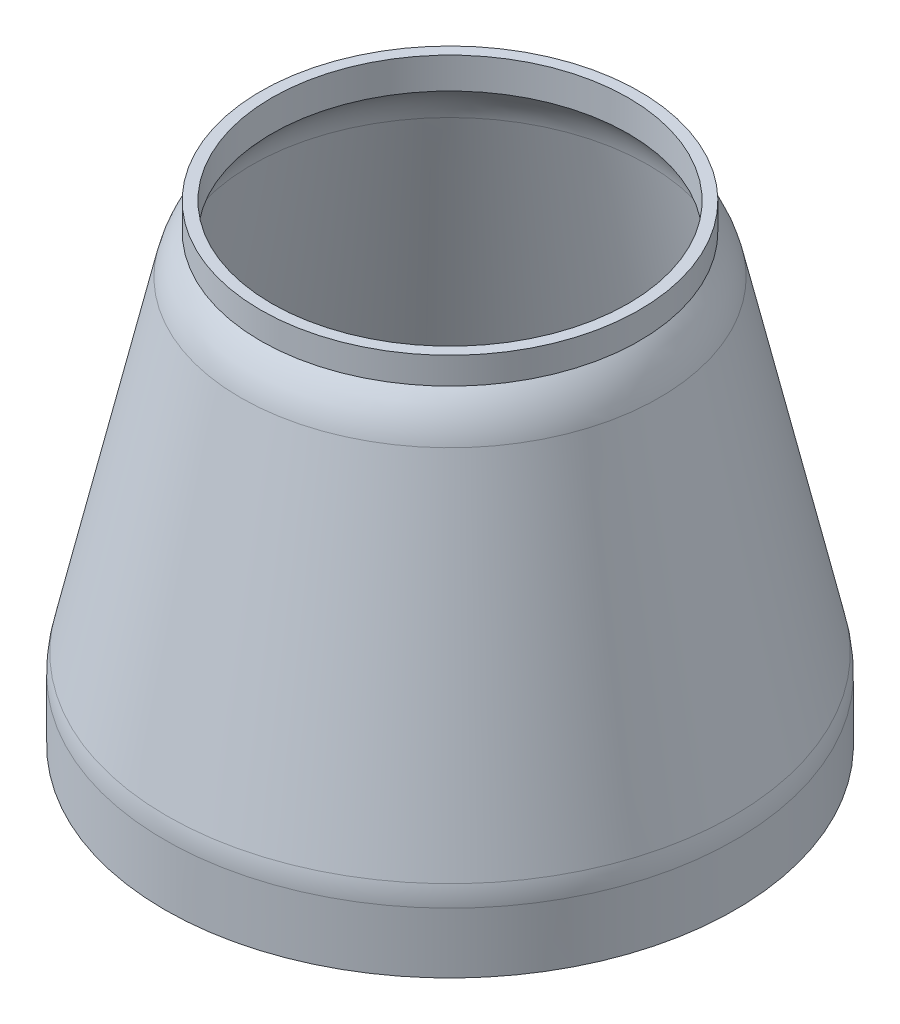
SolidWorks part; units mm, degrees
material "2024 Alloy"
ref_plane "Front Plane" through (0, 0, 0) normal (0, 0, 1) x (1, 0, 0)
ref_plane "Top Plane" through (0, 0, 0) normal (0, 1, 0) x (1, 0, 0)
ref_plane "Right Plane" through (0, 0, 0) normal (1, 0, 0) x (0, 0, -1)
sketch "Sketch1" plane through (0, 0, 0) normal (0, 1, 0) x (1, 0, 0)
  circle A1 centre (0, 0) radius 64
  circle A2 centre (0, 0) radius 64
  dimension "D2" = 128
  dimension "D3" = 128
extrude "Boss-Extrude1" add sketch "Sketch1" along normal blind 15.8 contours A1
ref_plane "Plane1" through (0, 99.8, 0) normal (0, 1, 0) x (1, 0, 0)
sketch "Sketch2" plane through (0, 99.8, 0) normal (0, 1, 0) x (1, 0, 0)
  circle A0 centre (0, 0) radius 45
  dimension "D1" = 90
loft "Loft1" add profiles "Sketch2" section edge at (0, 15.8, 64) section "Sketch2" connector at (-8.0213, 15.8, 63.4953) connector at (-12.7878, 99.8, 43.1448)
sketch "Sketch3" plane through (0, 99.8, 0) normal (0, 1, 0) x (1, 0, 0)
  circle A0 centre (0, 0) radius 42.5
  dimension "D1" = 85
extrude "Boss-Extrude2" add sketch "Sketch3" along normal blind 6
fillet "Fillet1" radius 20 2 edges at (0, 15.8, 64) (0, 99.8, 45)
sketch "Sketch4" plane through (0, 0, 0) normal (0, -1, 0) x (1, 0, 0)
  circle A0 centre (0, 0) radius 50
  dimension "D1" = 100
extrude "Cut-Extrude1" cut sketch "Sketch4" against normal blind 6 draft 20 contours A0
shell "Shell1" thickness 2.5 removed face at (0, 105.8, 42.5)
